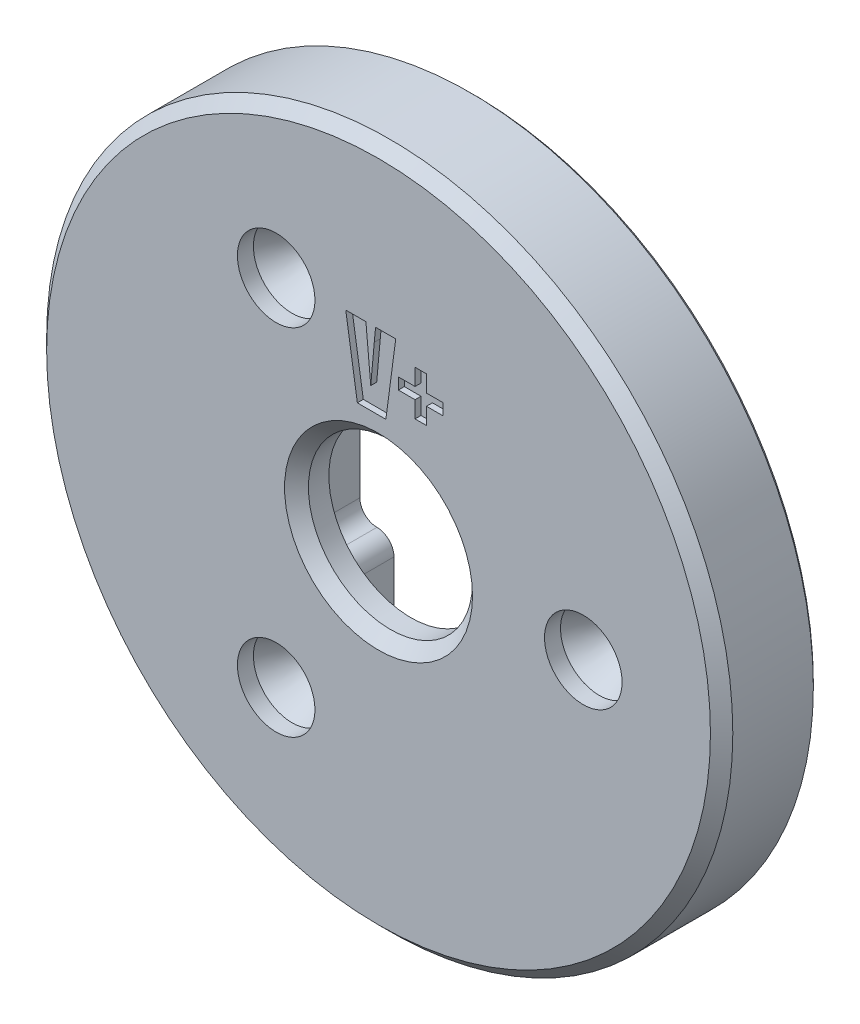
SolidWorks part; units mm, degrees
other "标注1"
sketch "草图9" plane through (123, 77, 0) normal (0.3334, -0.0407, -0.9419) x (-0.9427, 0, -0.3337)
material "有机玻璃 (TM) GS 丙烯酸铸钣"
ref_plane "前视基准面" through (0, 0, 0) normal (0, 0, 1) x (1, 0, 0)
ref_plane "上视基准面" through (0, 0, 0) normal (0, 1, 0) x (1, 0, 0)
ref_plane "右视基准面" through (0, 0, 0) normal (1, 0, 0) x (0, 0, -1)
sketch "草图2" plane through (0, 0, 0) normal (0, 0, 1) x (1, 0, 0)
  circle A2 centre (100, 100) radius 21.8
sketch "草图3" plane through (0, 0, 0) normal (0, 0, 1) x (1, 0, 0)
  circle A0 centre (100, 100) radius 23
extrude "凸台-拉伸3" add sketch "草图3" along normal blind 6.4
extrude "切除-拉伸1" cut sketch "草图2" along normal blind 1.63
sketch "草图4" plane through (0, 0, 0) normal (0, 0, 1) x (1, 0, 0)
  line L0 (83.312, 98.171) -> (83.312, 101.854)
  line L1 (83.566, 97.917) -> (86.868, 97.917)
  line L2 (87.122, 98.171) -> (87.122, 101.727)
  line L3 (83.566, 102.108) -> (86.741, 102.108)
  line L4 (98.171, 114.173) -> (98.171, 115.57)
  line L5 (96.901, 114.173) -> (98.171, 114.173)
  line L6 (96.393, 106.045) -> (96.393, 113.665)
  line L7 (93.98, 97.155) -> (93.98, 103.632)
  line L8 (96.266, 83.693) -> (96.266, 94.869)
  line L9 (96.901, 83.058) -> (102.489, 83.058)
  line L10 (103.759, 84.328) -> (106.807, 84.328)
  line L11 (107.188, 84.709) -> (108.712, 84.709)
  line L12 (109.347, 85.344) -> (109.347, 86.868)
  line L13 (109.855, 87.376) -> (110.871, 87.376)
  line L14 (111.379, 87.884) -> (111.379, 88.646)
  line L15 (111.887, 89.154) -> (114.046, 89.154)
  line L16 (114.554, 89.662) -> (114.554, 91.059)
  line L17 (115.062, 91.567) -> (115.189, 91.567)
  line L18 (115.824, 92.202) -> (115.824, 94.615)
  line L19 (106.299, 94.869) -> (115.57, 94.869)
  line L20 (105.791, 95.377) -> (105.791, 102.616)
  line L21 (106.426, 103.251) -> (115.443, 103.251)
  line L22 (116.586, 102.108) -> (117.983, 102.108)
  line L23 (118.237, 102.362) -> (118.237, 102.997)
  line L24 (116.713, 104.521) -> (116.713, 109.093)
  line L25 (111.252, 109.855) -> (115.951, 109.855)
  line L26 (110.744, 110.363) -> (110.744, 113.411)
  line L27 (103.632, 114.427) -> (109.728, 114.427)
  line L28 (103.251, 114.808) -> (103.251, 115.57)
  line L29 (98.552, 115.951) -> (102.87, 115.951)
  arc A60 (83.566, 102.108) -> (83.312, 101.854) centre (83.566, 101.854) ccw
  arc A63 (83.312, 98.171) -> (83.566, 97.917) centre (83.566, 98.171) ccw
  arc A66 (86.868, 97.917) -> (87.122, 98.171) centre (86.868, 98.171) ccw
  arc A69 (87.122, 101.727) -> (86.741, 102.108) centre (86.741, 101.727) ccw
  arc A72 (98.552, 115.951) -> (98.171, 115.57) centre (98.552, 115.57) ccw
  arc A75 (96.901, 114.173) -> (96.393, 113.665) centre (96.901, 113.665) ccw
  arc A78 (95.25, 104.902) -> (96.393, 106.045) centre (95.25, 106.045) ccw
  arc A81 (95.25, 104.902) -> (93.98, 103.632) centre (95.25, 103.632) ccw
  arc A84 (93.98, 97.155) -> (95.123, 96.012) centre (95.123, 97.155) ccw
  arc A87 (96.266, 94.869) -> (95.123, 96.012) centre (95.123, 94.869) ccw
  arc A90 (96.266, 83.693) -> (96.901, 83.058) centre (96.901, 83.693) ccw
  arc A93 (102.489, 83.058) -> (102.87, 83.439) centre (102.489, 83.439) ccw
  arc A96 (103.759, 84.328) -> (102.87, 83.439) centre (103.759, 83.439) ccw
  arc A99 (106.807, 84.328) -> (106.934, 84.455) centre (106.807, 84.455) ccw
  arc A102 (107.188, 84.709) -> (106.934, 84.455) centre (107.188, 84.455) ccw
  arc A105 (108.712, 84.709) -> (109.347, 85.344) centre (108.712, 85.344) ccw
  arc A108 (109.855, 87.376) -> (109.347, 86.868) centre (109.855, 86.868) ccw
  arc A111 (110.871, 87.376) -> (111.379, 87.884) centre (110.871, 87.884) ccw
  arc A114 (111.887, 89.154) -> (111.379, 88.646) centre (111.887, 88.646) ccw
  arc A117 (114.046, 89.154) -> (114.554, 89.662) centre (114.046, 89.662) ccw
  arc A120 (115.062, 91.567) -> (114.554, 91.059) centre (115.062, 91.059) ccw
  arc A123 (115.189, 91.567) -> (115.824, 92.202) centre (115.189, 92.202) ccw
  arc A126 (115.824, 94.615) -> (115.57, 94.869) centre (115.57, 94.615) ccw
  arc A129 (105.791, 95.377) -> (106.299, 94.869) centre (106.299, 95.377) ccw
  arc A132 (106.426, 103.251) -> (105.791, 102.616) centre (106.426, 102.616) ccw
  arc A135 (116.078, 102.616) -> (115.443, 103.251) centre (115.443, 102.616) ccw
  arc A138 (116.078, 102.616) -> (116.586, 102.108) centre (116.586, 102.616) ccw
  arc A141 (117.983, 102.108) -> (118.237, 102.362) centre (117.983, 102.362) ccw
  arc A144 (118.237, 102.997) -> (117.729, 103.505) centre (117.729, 102.997) ccw
  arc A147 (116.713, 104.521) -> (117.729, 103.505) centre (117.729, 104.521) ccw
  arc A150 (116.713, 109.093) -> (115.951, 109.855) centre (115.951, 109.093) ccw
  arc A153 (110.744, 110.363) -> (111.252, 109.855) centre (111.252, 110.363) ccw
  arc A156 (110.744, 113.411) -> (109.728, 114.427) centre (109.728, 113.411) ccw
  arc A159 (103.251, 114.808) -> (103.632, 114.427) centre (103.632, 114.808) ccw
  arc A162 (103.251, 115.57) -> (102.87, 115.951) centre (102.87, 115.57) ccw
extrude "切除-拉伸2" cut sketch "草图4" along normal blind 2.6 from surface contours A162 L29 A72 L4 L5 A75 L6 A78 A81 L7 A84 A87 L8 A90 L9 A93 A96 L10 A99 A102 L11 A105 L12 A108 L13 region at (104.0257, 99.7178, 0) starting at face at (121.8, 100, 1.63)
sketch "草图5" plane through (0, 0, 0) normal (0, 0, 1) x (1, 0, 0)
  circle A0 centre (113.725, 100) radius 1.35
  circle A3 centre (93.1375, 88.1138) radius 1.35
  circle A6 centre (93.1375, 111.8862) radius 1.35
  circle A9 centre (100, 100) radius 5.5
extrude "切除-拉伸3" cut sketch "草图5" along normal up to surface (6.4 mm away) from surface contours A0 | A6 | A3 | A6 region at (113.725, 100, 0) region at (93.1375, 88.1138, 0) region at (93.1375, 111.8862, 0) up to face at (123, 100, 6.4) starting at face at (121.8, 100, 1.63)
extrude "切除-拉伸4" cut sketch "草图5<3>" along normal up to surface (6.4 mm away) from surface contours A9 region at (100, 100, 0) up to face at (115.075, 100, 6.4) starting at face at (107.6312, 98.717, 4.23)
sketch "草图5<3>" plane through (0, 0, 0) normal (0, 0, 1) x (1, 0, 0) same geometry as "草图5"
chamfer "倒角1" distance 0.75 angle 45 1 edges at (123, 100, 6.4)
sketch "草图6" plane through (0, 0, 0) normal (0, 0, 1) x (1, 0, 0)
  circle A0 centre (93.1375, 111.8862) radius 2.6
  circle A1 centre (93.1375, 88.1138) radius 2.6
  circle A2 centre (113.725, 100) radius 2.6
extrude "切除-拉伸5" cut sketch "草图6" against normal blind 1 from surface starting at face at (122.25, 100, 6.4)
chamfer "倒角2" distance 1.29 distance2 2.385 3 edges at (115.075, 100, 5.4) (94.4875, 88.1138, 5.4) (94.4875, 111.8862, 5.4) first distance on face at (115.075, 100, 5.4) first distance on face at (94.4875, 88.1138, 5.4) first distance on face at (94.4875, 111.8862, 5.4)
chamfer "倒角3" distance 0.25 angle 45 2 edges at (123, 100, 0) (121.8, 100, 0)
chamfer "倒角4" distance 0.8 1 edges at (105.5, 100, 6.4)
sketch "草图7" plane through (0, 0, 0) normal (0, 0, 1) x (1, 0, 0)
  text T0 "V+" font "Impact" height 5
extrude "切除-拉伸7" cut sketch "草图7" against normal blind 0.4 from surface starting at face at (106.3, 100, 6.4)
sketch "草图8" plane through (0, 0, 0) normal (0, 0, 1) x (1, 0, 0)
  line L0 (82.169, 102.87) -> (83.058, 102.87)
  line L1 (83.058, 102.87) -> (83.439, 102.489)
  line L2 (83.439, 98.425) -> (83.439, 102.489)
  line L3 (83.439, 98.425) -> (83.82, 98.044)
  line L4 (83.82, 98.044) -> (86.868, 98.044)
  line L5 (86.868, 98.044) -> (87.122, 98.298)
  line L6 (87.122, 98.298) -> (87.122, 101.981)
  line L7 (87.122, 101.981) -> (87.376, 102.235)
  line L8 (87.376, 102.235) -> (91.313, 102.235)
  line L9 (91.313, 102.235) -> (91.567, 102.489)
  line L10 (91.567, 102.489) -> (91.567, 107.95)
  line L11 (91.186, 108.331) -> (91.567, 107.95)
  line L12 (88.5926, 108.331) -> (91.186, 108.331)
  line L13 (87.8407, 109.0829) -> (88.5926, 108.331)
  line L14 (85.3763, 109.0829) -> (87.8407, 109.0829)
  line L15 (85.217, 108.9236) -> (85.3763, 109.0829)
  line L16 (85.217, 108.077) -> (85.217, 108.9236)
  line L17 (84.836, 107.696) -> (85.217, 108.077)
  line L18 (83.185, 107.696) -> (84.836, 107.696)
  line L19 (82.169, 106.68) -> (83.185, 107.696)
  line L20 (82.169, 102.87) -> (82.169, 106.68)
extrude "切除-拉伸8" cut sketch "草图8" along normal blind 1.5 from surface starting at face at (115.075, 100, 1.63)
